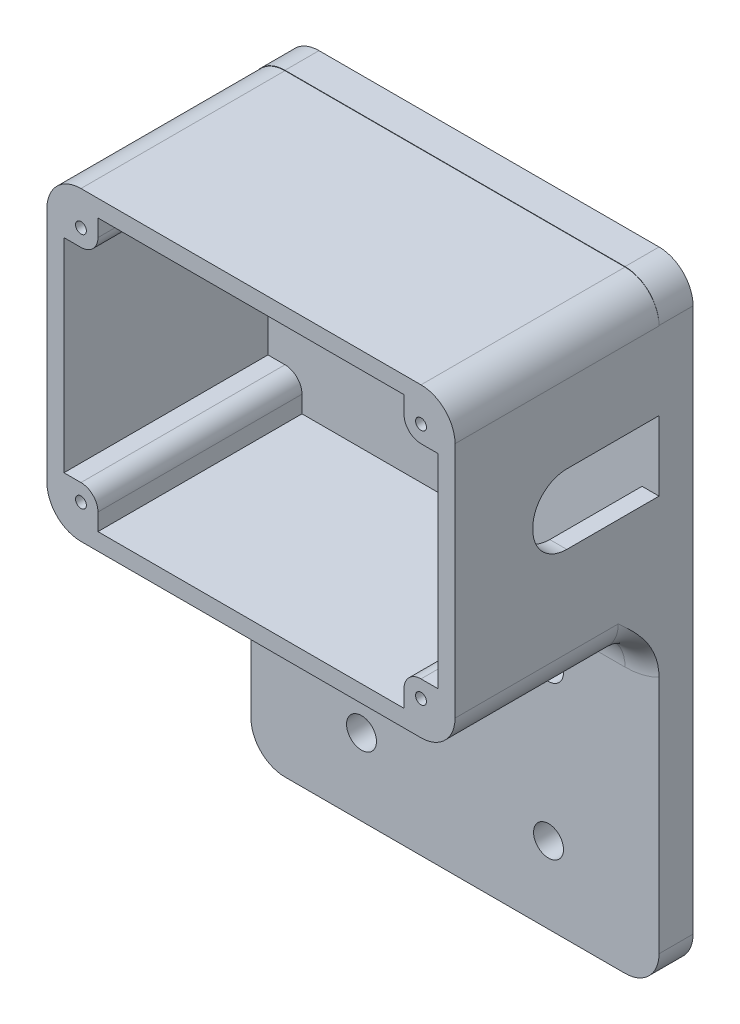
SolidWorks part; units mm, degrees
ref_plane "Front Plane" through (0, 0, 0) normal (0, 0, 1) x (1, 0, 0)
ref_plane "Top Plane" through (0, 0, 0) normal (0, 1, 0) x (1, 0, 0)
ref_plane "Right Plane" through (0, 0, 0) normal (1, 0, 0) x (0, 0, -1)
sketch "Sketch1" plane through (0, 0, 0) normal (0, 0, 1) x (1, 0, 0)
  line L0 (-27.5, 90) -> (-27.5, -90) construction
  line L1 (-50, 90) -> (50, 90)
  line L2 (-60, 80) -> (-60, -80)
  line L3 (-50, -90) -> (50, -90)
  line L4 (60, 80) -> (60, -80)
  line L5 (-60, 90) -> (60, -90) construction
  line L6 (-60, -90) -> (60, 90) construction
  line L7 (27.5, 90) -> (27.5, -90) construction
  line L8 (-60, -22.5) -> (60, -22.5) construction
  line L9 (-60, -67.5) -> (60, -67.5) construction
  arc A0 (-60, -80) -> (-50, -90) centre (-50, -80) ccw
  arc A1 (50, -90) -> (60, -80) centre (50, -80) ccw
  arc A2 (60, 80) -> (50, 90) centre (50, 80) ccw
  arc A3 (-50, 90) -> (-60, 80) centre (-50, 80) ccw
  circle A4 centre (-27.5, -22.5) radius 4.4
  circle A5 centre (27.5, -22.5) radius 4.4
  circle A6 centre (-27.5, -67.5) radius 4.4
  circle A7 centre (27.5, -67.5) radius 4.4
  point P0 (0, 0)
  dimension "D3" = 10
  dimension "D1" = 120
  dimension "D2" = 180
  dimension "D4" = 45
  dimension "D5" = 22.5
  dimension "D6" = 32.5
  dimension "D7" = 32.5
extrude "Boss-Extrude1" add sketch "Sketch1" along normal blind 10
sketch "Sketch2" plane through (0, 0, 10) normal (0, 0, 1) x (1, 0, 0)
  line L0 (-50, 0) -> (50, 0)
  line L1 (-45, 10) -> (-45, 5)
  line L2 (-50, 15) -> (-55, 15)
  line L3 (60, 10) -> (60, 79.8877)
  line L4 (50, 89.8877) -> (-50, 89.8877)
  line L5 (-60, 79.8877) -> (-60, 10)
  line L6 (-45, 5) -> (45, 5)
  line L7 (55, 15) -> (55, 74.8877)
  line L8 (45, 84.8877) -> (-45, 84.8877)
  line L9 (-55, 74.8877) -> (-55, 15)
  line L10 (-45, 79.8877) -> (-45, 84.8877)
  line L11 (-50, 74.8877) -> (-55, 74.8877)
  line L12 (45, 10) -> (45, 5)
  line L13 (50, 15) -> (55, 15)
  line L14 (45, 79.8877) -> (45, 84.8877)
  line L15 (50, 74.8877) -> (55, 74.8877)
  line L16 (50, 84.8877) -> (-50, 84.8877) construction
  line L17 (55, 10) -> (55, 79.8877) construction
  line L18 (-50, 5) -> (50, 5) construction
  line L19 (-55, 79.8877) -> (-55, 10) construction
  arc A0 (-60, 10) -> (-50, 0) centre (-50, 10) ccw
  arc A1 (60, 10) -> (50, 0) centre (50, 10) cw
  arc A2 (60, 79.8877) -> (50, 89.8877) centre (50, 79.8877) ccw
  arc A3 (-50, 89.8877) -> (-60, 79.8877) centre (-50, 79.8877) ccw
  arc A9 (50, 15) -> (45, 10) centre (50, 10) ccw
  arc A10 (45, 79.8877) -> (50, 74.8877) centre (50, 79.8877) ccw
  arc A11 (-50, 74.8877) -> (-45, 79.8877) centre (-50, 79.8877) ccw
  arc A12 (55, 79.8877) -> (50, 84.8877) centre (50, 79.8877) ccw construction
  arc A13 (-45, 10) -> (-50, 15) centre (-50, 10) ccw
  arc A14 (55, 10) -> (50, 5) centre (50, 10) cw construction
  arc A15 (-55, 10) -> (-50, 5) centre (-50, 10) ccw construction
  arc A16 (-50, 84.8877) -> (-55, 79.8877) centre (-50, 79.8877) ccw construction
  circle A17 centre (-50, 79.8877) radius 1.6
  circle A18 centre (-50, 10) radius 1.6
  circle A19 centre (50, 10) radius 1.6
  circle A20 centre (50, 79.8877) radius 1.6
  dimension "D1" = 5
extrude "Boss-Extrude2" add sketch "Sketch2" along normal blind 60
fillet "Fillet1" radius 12 1 edges at (0, 0, 10) type face fillet first side face at (0, 0, 40) second side face at (0, -41.0355, 10)
sketch "Sketch3" plane through (60, 0, 0) normal (1, 0, 0) x (0, 0, -1)
  line L0 (-10, 79.8877) -> (-10, 10) construction
  line L1 (-70, 79.8877) -> (-10, 79.8877) construction
  line L2 (-70, 10) -> (-22, 10) construction
  line L3 (0, -80) -> (0, 80) construction
  line L5 (-10, 57.0428) -> (-37.1307, 57.0428)
  line L6 (-10, 57.0428) -> (-10, 36.544)
  line L7 (-10, 36.544) -> (-37.1307, 36.544)
  line L8 (-47.1307, 47.0428) -> (-47.1307, 46.544)
  arc A0 (-37.1307, 36.544) -> (-47.1307, 46.544) centre (-37.1307, 46.544) cw
  arc A1 (-47.1307, 47.0428) -> (-37.1307, 57.0428) centre (-37.1307, 47.0428) cw
  dimension "D2" = 10
  dimension "D1" = 10
extrude "Cut-Extrude1" cut sketch "Sketch3" against normal up to surface (5 mm away) up to face at (55, 44.9438, 40)
sketch "Sketch4" plane through (0, 0, 70) normal (0, 0, 1) x (1, 0, 0)
  line L1 (-50, 0.202) -> (50, 0.202)
  line L2 (-60, 10.202) -> (-60, 80)
  line L3 (-50, 90) -> (50, 90)
  line L4 (60, 10.202) -> (60, 80)
  arc A0 (-50, 0.202) -> (-60, 10.202) centre (-50, 10.202) cw
  arc A1 (50, 0.202) -> (60, 10.202) centre (50, 10.202) ccw
  arc A2 (60, 80) -> (50, 90) centre (50, 80) ccw
  arc A3 (-50, 90) -> (-60, 80) centre (-50, 80) ccw
  circle A4 centre (-50, 79.8877) radius 1.9
  circle A5 centre (50, 79.8877) radius 1.9
  circle A6 centre (50, 10) radius 1.9
  circle A7 centre (-50, 10) radius 1.9
  point P8 (-60, 0.202)
